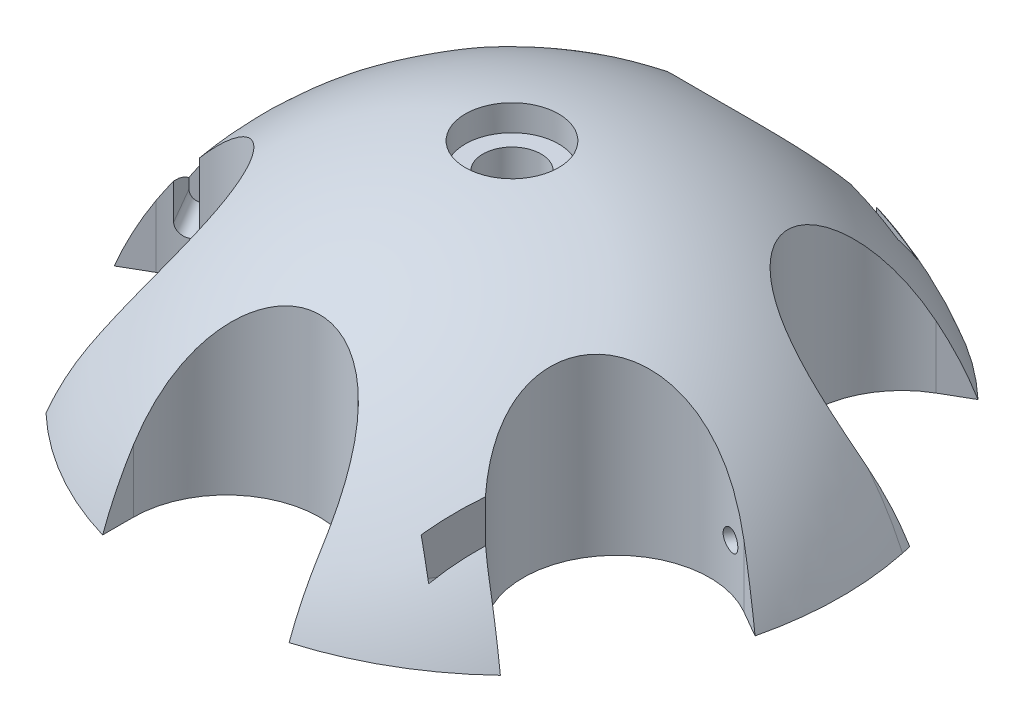
SolidWorks part; units mm, degrees
ref_plane "Front Plane" through (0, 0, 0) normal (0, 0, 1) x (1, 0, 0)
ref_plane "Top Plane" through (0, 0, 0) normal (0, 1, 0) x (1, 0, 0)
ref_plane "Right Plane" through (0, 0, 0) normal (1, 0, 0) x (0, 0, -1)
sketch "Sketch1" plane through (0, 0, 0) normal (0, 0, 1) x (1, 0, 0)
  line L0 (0, 60) -> (0, -60) construction
  line L1 (0, 60) -> (0, -60)
  arc A0 (0, 60) -> (0, -60) centre (0, 0) ccw
  dimension "D1" = 60
revolve "Revolve1" add sketch "Sketch1" angle 360 about L0
ref_plane "Plane4" through (0, 20, 0) normal (0, 1, 0) x (1, 0, 0)
sketch "Sketch2" plane through (0, 20, 0) normal (0, 1, 0) x (1, 0, 0)
  circle A0 centre (0, 0) radius 80.0525
extrude "Cut-Extrude1" cut sketch "Sketch2" against normal through all
ref_axis "Axis2" through (0, 0, 0) along (0, -1, 0)
ref_plane "Plane5" through (0, 0, 0) normal (-0.866, 0, 0.5) x (0, -1, 0)
ref_plane "Plane6" through (0, 0, 0) normal (-0.866, 0, -0.5) x (0, -1, 0)
ref_plane "Plane7" through (0, 0, 0) normal (0, 0, -1) x (0, -1, 0)
sketch "Sketch4" plane through (0, 0, 0) normal (0, 0, -1) x (0, -1, 0)
  line L0 (-20, 62.2254) -> (-20, -62.2254) construction
  arc A0 (-20, 56.5685) -> (-60, 0) centre (0, 0) ccw
  arc A1 (-20, 56.5685) -> (-20, -56.5685) centre (0, 0) ccw construction
  point P9 (-20, 56.5685)
sketch "Sketch5" plane through (0, 0, 0) normal (-0.866, 0, -0.5) x (0, -1, 0)
  line L0 (-20, 62.2254) -> (-20, -62.2254) construction
  arc A0 (-20, 56.5685) -> (-60, 0) centre (0, 0) ccw
  arc A1 (-20, 56.5685) -> (-20, -56.5685) centre (0, 0) ccw construction
  ellipse E0 centre (0, 0) end of major axis (-60, 0) minor radius 30 (-20, 28.2843) -> (-60, 0) ccw construction
  point P16 (-20, 56.5685)
sketch "Sketch6" plane through (0, 20, 0) normal (0, -1, 0) x (1, 0, 0)
  line L0 (-28.2843, 48.9898) -> (-56.5685, 0) construction
  line L1 (-28.2843, 48.9898) -> (0, 0) construction
  line L2 (-56.5685, 0) -> (0, 0) construction
  line L3 (-29.04, 0) -> (29.04, 0) construction
  line L4 (-42.4264, 24.4949) -> (0, 0) construction
  line L6 (-34.4264, 38.3513) -> (-45.7062, 44.8637)
  line L7 (-50.4264, 10.6385) -> (-61.7062, 17.1509)
  line L8 (-61.7062, 17.1509) -> (-45.7062, 44.8637)
  circle A0 centre (0, 0) radius 56.5685 construction
  arc A1 (-50.4264, 10.6385) -> (-34.4264, 38.3513) centre (-42.4264, 24.4949) ccw
  dimension "D1" = 16
extrude "Cut-Extrude2" cut sketch "Sketch6" against normal through all
pattern_circular "CirPattern1" count 6 over 360 about axis through (0, 0, 0) along (0, -1, 0) of "Cut-Extrude2"
sketch "Sketch7" plane through (8, 0, 13.8564) normal (-0.5, 0, -0.866) x (-0.866, 0, 0.5)
  line L0 (32.9898, 20) -> (48.9898, 20) construction
  line L1 (0, 0) -> (0, -52.8) construction
  circle A0 centre (45, 28) radius 1.75
  dimension "D1" = 3.5
  dimension "D2" = 8
  dimension "D3" = 45
extrude "Cut-Extrude3" cut sketch "Sketch7" against normal blind 3 and the other way blind 39
ref_plane "Plane11" through (0, 0, 0) normal (-0.5, 0, -0.866) x (-0.866, 0, 0.5)
sketch "Sketch11" plane through (0, 0, 0) normal (-0.5, 0, -0.866) x (-0.866, 0, 0.5)
  line L0 (46.75, 28) -> (46.75, 40.6459)
  line L1 (46.75, 40.6459) -> (43.25, 40.6459)
  line L2 (43.25, 40.6459) -> (43.25, 28)
  line L3 (43.25, 28) -> (49.1515, 28) construction
  arc A0 (43.25, 28) -> (46.75, 28) centre (45, 28) ccw
  dimension "D1" = 3.5
extrude "Cut-Extrude5" cut sketch "Sketch11" along normal up to surface (23 mm away) up to face at (-51.9867, 28, 3.4564)
pattern_circular "CirPattern2" count 3 over 360 about axis through (0, 0, 0) along (0, -1, 0) of "Cut-Extrude5", "Cut-Extrude3"
sketch "Sketch12" plane through (0, 20, 0) normal (0, -1, 0) x (1, 0, 0)
  line L1 (15.5885, -27) -> (31.1769, 0)
  line L2 (31.1769, 0) -> (15.5885, 27)
  line L3 (15.5885, 27) -> (-15.5885, 27)
  line L4 (-15.5885, 27) -> (-31.1769, 0)
  line L5 (-31.1769, 0) -> (-15.5885, -27)
  line L6 (-15.5885, -27) -> (15.5885, -27)
  circle A0 centre (0, 0) radius 27 construction
  dimension "D1" = 54
extrude "Cut-Extrude6" cut sketch "Sketch12" against normal blind 5
ref_plane "Plane12" through (0, 60, 0) normal (0, 1, 0) x (1, 0, 0)
sketch "Sketch13" plane through (0, 60, 0) normal (0, 1, 0) x (1, 0, 0)
  circle A0 centre (0, 0) radius 5
  dimension "D1" = 10
extrude "Cut-Extrude7" cut sketch "Sketch13" against normal through all
sketch "Sketch14" plane through (0, 60, 0) normal (0, 1, 0) x (1, 0, 0)
  circle A0 centre (0, 0) radius 8
  dimension "D1" = 16
extrude "Cut-Extrude8" cut sketch "Sketch14" against normal blind 5
